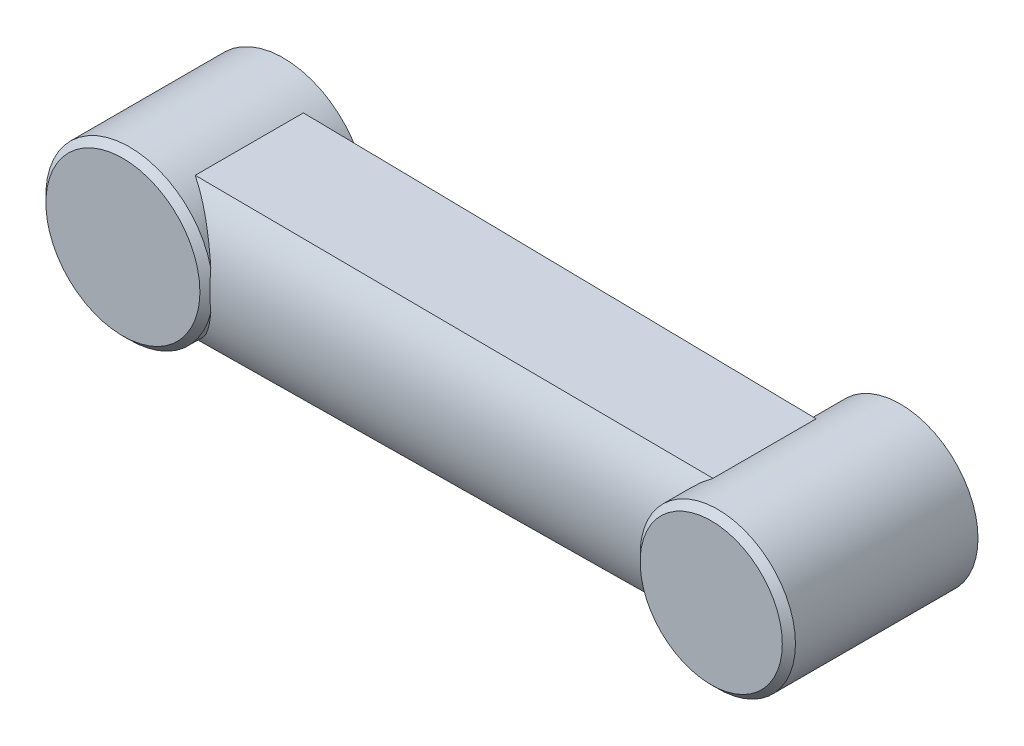
SolidWorks part; units mm, degrees
ref_plane "Front Plane" through (0, 0, 0) normal (0, 0, 1) x (1, 0, 0)
ref_plane "Top Plane" through (0, 0, 0) normal (0, 1, 0) x (1, 0, 0)
ref_plane "Right Plane" through (0, 0, 0) normal (1, 0, 0) x (0, 0, -1)
sketch "Sketch1" plane through (0, 0, 0) normal (0, 0, 1) x (1, 0, 0)
  circle A0 centre (0, 0) radius 63.5
  dimension "D1" = 127
extrude "Boss-Extrude1" add sketch "Sketch1" along normal blind 61 and the other way blind 61
chamfer "Chamfer1" distance 5 angle 45 1 edges at (63.5, 0, 61)
ref_plane "Plane2" through (63.5, 0, 0) normal (1, 0, 0) x (0, 0, -1)
ref_plane "Plane1" through (398.5, 0, 0) normal (1, 0, 0) x (0, 0, -1)
ref_plane "Plane3" through (457.5, 0, 0) normal (1, 0, 0) x (0, 0, -1)
ref_plane "Plane4" through (0, 0, 72.5) normal (0, 0, 1) x (1, 0, 0)
sketch "Sketch6" plane through (0, 0, 0) normal (-1, 0, 0) x (0, 0, 1)
  line L6 (40, -54) -> (-42.5, -54)
  line L7 (-42.5, 54) -> (40, 54)
  arc A5 (-42.5, 54) -> (-42.5, -54) centre (44.9479, 0) ccw
  arc A6 (40, 54) -> (40, -54) centre (-34.1011, 0) cw
sketch "Sketch7" plane through (457.5, 0, 59) normal (-1, 0, 0) x (0, 0, 1)
  line L0 (-19.9754, -49.884) -> (-98.0246, -49.884)
  line L6 (-98.0246, 49.884) -> (-19.9754, 49.884)
  line L7 (-98.0246, 49.884) -> (-19.9754, -49.884) construction
  arc A9 (-98.0246, 49.884) -> (-98.0246, -49.884) centre (-12.9036, 0) ccw
  arc A10 (-19.9754, 49.884) -> (-19.9754, -49.884) centre (-91.9525, 0) cw
loft "Loft1" add profiles "Sketch6", "Sketch7" start constraint default end constraint default
sketch "Sketch9" plane through (0, 0, 0) normal (0, 0, 1) x (1, 0, 0)
  line L0 (457.5, -49.884) -> (457.5, 49.884) construction
  circle A0 centre (457.5, 0) radius 59
extrude "Boss-Extrude2" add sketch "Sketch9" along normal blind 71.5 and the other way blind 72.2
ref_axis "Axis1" through (0, 0, 56) along (0, 0, -1)
chamfer "Chamfer2" distance 5 angle 45 1 edges at (516.5, 0, 71.5)
